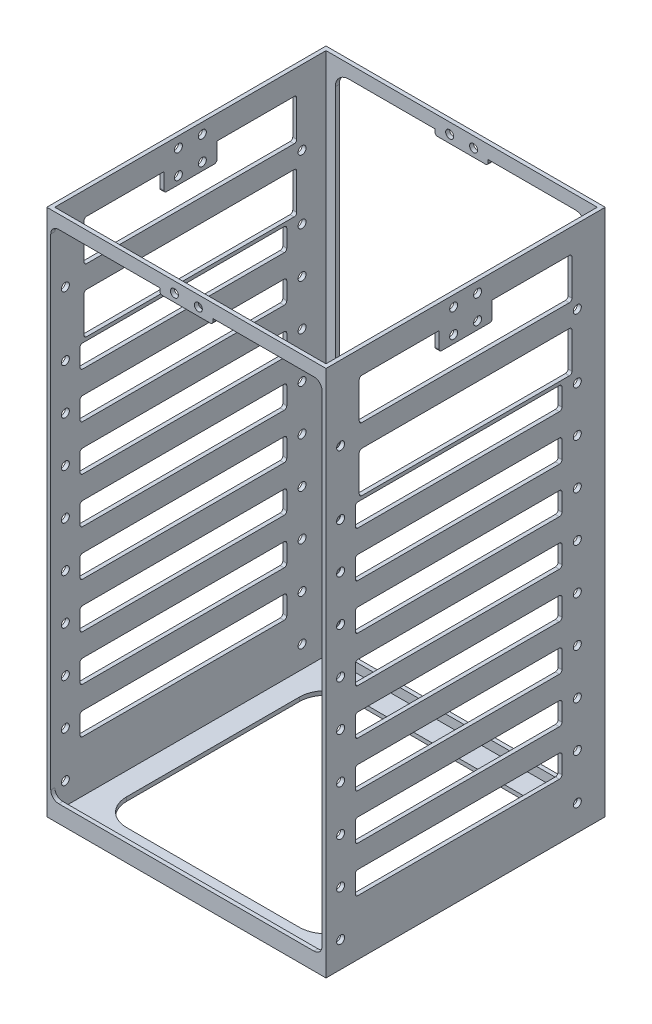
SolidWorks part; units mm, degrees
ref_plane "Front Plane" through (0, 0, 0) normal (0, 0, 1) x (1, 0, 0)
ref_plane "Top Plane" through (0, 0, 0) normal (0, 1, 0) x (1, 0, 0)
ref_plane "Right Plane" through (0, 0, 0) normal (1, 0, 0) x (0, 0, -1)
sketch "Sketch1" plane through (0, 0, 0) normal (0, 1, 0) x (1, 0, 0)
  line L1 (-52.5, -52.5) -> (52.5, -52.5)
  line L2 (-52.5, -52.5) -> (-52.5, 52.5)
  line L3 (-52.5, 52.5) -> (52.5, 52.5)
  line L4 (52.5, -52.5) -> (52.5, 52.5)
  line L5 (-52.5, -52.5) -> (52.5, 52.5) construction
  line L6 (-52.5, 52.5) -> (52.5, -52.5) construction
  line L7 (-32.5, -42.5) -> (32.5, -42.5)
  line L8 (-42.5, -32.5) -> (-42.5, 32.5)
  line L9 (-32.5, 42.5) -> (32.5, 42.5)
  line L10 (42.5, -32.5) -> (42.5, 32.5)
  line L11 (-42.5, -42.5) -> (42.5, 42.5) construction
  line L12 (-42.5, 42.5) -> (42.5, -42.5) construction
  arc A0 (32.5, -42.5) -> (42.5, -32.5) centre (32.5, -32.5) ccw
  arc A1 (32.5, 42.5) -> (42.5, 32.5) centre (32.5, 32.5) cw
  arc A2 (-42.5, 32.5) -> (-32.5, 42.5) centre (-32.5, 32.5) cw
  arc A3 (-32.5, -42.5) -> (-42.5, -32.5) centre (-32.5, -32.5) cw
  point P0 (0, 0)
  point P6 (0, 0)
  dimension "D3" = 10
  dimension "D1" = 105
  dimension "D2" = 42.5
extrude "Boss-Extrude2" add sketch "Sketch1" along normal blind 1.5 contours A3 L7 A0 L10 A1 L9 A2 L8 | L2 L1 L4 L3 region at (0, 0, 0)
sketch "Sketch3" plane through (0, 1.5, 0) normal (0, 1, 0) x (1, 0, 0)
  line L1 (-52.5, -52.5) -> (52.5, -52.5)
  line L2 (-52.5, -52.5) -> (-52.5, 52.5)
  line L3 (-52.5, 52.5) -> (52.5, 52.5)
  line L4 (52.5, -52.5) -> (52.5, 52.5)
  line L5 (-52.5, -52.5) -> (52.5, 52.5) construction
  line L6 (-52.5, 52.5) -> (52.5, -52.5) construction
  line L7 (-51, -51) -> (51, -51)
  line L8 (-51, -51) -> (-51, 51)
  line L9 (-51, 51) -> (51, 51)
  line L10 (51, -51) -> (51, 51)
  line L11 (-51, -51) -> (51, 51) construction
  line L12 (-51, 51) -> (51, -51) construction
  point P0 (0, 0)
  point P7 (0, 0)
  dimension "D1" = 1.5
extrude "Boss-Extrude3" add sketch "Sketch3" along normal blind 197 contours L8 L7 L10 L9 | L2 L3 L4 L1
sketch "Sketch4" plane through (0, 0, -52.5) normal (0, 0, 1) x (1, 0, 0)
  line L0 (-52.5, 0) -> (52.5, 0) construction
  line L1 (-42.5, 5) -> (42.5, 5)
  line L2 (-47.5, 10) -> (-47.5, 188.5)
  line L3 (-42.5, 193.5) -> (42.5, 193.5)
  line L4 (47.5, 10) -> (47.5, 188.5)
  line L5 (-47.5, 5) -> (47.5, 193.5) construction
  line L6 (-47.5, 193.5) -> (47.5, 5) construction
  line L7 (52.5, 198.5) -> (52.5, 0) construction
  line L8 (-51, 198.5) -> (51, 198.5) construction
  line L9 (-52.5, 198.5) -> (-52.5, 0) construction
  arc A0 (-42.5, 5) -> (-47.5, 10) centre (-42.5, 10) cw
  arc A1 (42.5, 5) -> (47.5, 10) centre (42.5, 10) ccw
  arc A2 (42.5, 193.5) -> (47.5, 188.5) centre (42.5, 188.5) cw
  arc A3 (-47.5, 188.5) -> (-42.5, 193.5) centre (-42.5, 188.5) cw
  point P0 (0, 99.25)
  dimension "D5" = 5
  dimension "D1" = 5
  dimension "D2" = 5
  dimension "D3" = 5
  dimension "D4" = 5
extrude "Cut-Extrude1" cut sketch "Sketch4" along normal up to surface (1.5 mm away) up to face at (0, 100, -51)
sketch "Sketch5" plane through (0, 0, 52.5) normal (0, 0, 1) x (1, 0, 0)
  line L0 (-52.5, 198.5) -> (52.5, 198.5) construction
  line L1 (-48, 6.5) -> (48, 6.5)
  line L2 (-51, 9.5) -> (-51, 190.5)
  line L3 (-48, 193.5) -> (48, 193.5)
  line L4 (51, 9.5) -> (51, 190.5)
  line L5 (-51, 6.5) -> (51, 193.5) construction
  line L6 (-51, 193.5) -> (51, 6.5) construction
  line L7 (-52.5, 1.5) -> (52.5, 1.5) construction
  line L8 (-52.5, 198.5) -> (-52.5, 0) construction
  line L9 (52.5, 198.5) -> (52.5, 0) construction
  arc A0 (48, 6.5) -> (51, 9.5) centre (48, 9.5) ccw
  arc A1 (-48, 6.5) -> (-51, 9.5) centre (-48, 9.5) cw
  arc A2 (48, 193.5) -> (51, 190.5) centre (48, 190.5) cw
  arc A3 (-51, 190.5) -> (-48, 193.5) centre (-48, 190.5) cw
  point P0 (0, 100)
  dimension "D5" = 3
  dimension "D1" = 5
  dimension "D2" = 5
  dimension "D3" = 1.5
  dimension "D4" = 1.5
sketch "Sketch6" plane through (52.5, 0, 0) normal (1, 0, 0) x (0, 0, -1)
  line L0 (-52.5, 6.5) -> (-52.5, 193.5) construction
  line L2 (-52.5, 0) -> (52.5, 0) construction
  circle A0 centre (-47, 9.75) radius 1.5
  circle A1 centre (42, 9.75) radius 1.5
  circle A2 centre (-47, 26.85) radius 1.5
  circle A3 centre (42, 26.85) radius 1.5
  circle A4 centre (-47, 43.95) radius 1.5
  circle A5 centre (42, 43.95) radius 1.5
  circle A6 centre (-47, 61.05) radius 1.5
  circle A7 centre (42, 61.05) radius 1.5
  circle A8 centre (-47, 78.15) radius 1.5
  circle A9 centre (42, 78.15) radius 1.5
  circle A10 centre (-47, 95.25) radius 1.5
  circle A11 centre (42, 95.25) radius 1.5
  circle A12 centre (-47, 112.35) radius 1.5
  circle A13 centre (42, 112.35) radius 1.5
  circle A14 centre (-47, 129.45) radius 1.5
  circle A15 centre (42, 129.45) radius 1.5
  circle A16 centre (-47, 146.55) radius 1.5
  circle A17 centre (42, 146.55) radius 1.5
  circle A18 centre (-47, 170.55) radius 1.5
  circle A19 centre (42, 170.55) radius 1.5
  dimension "D4" = 3
  dimension "D5" = 3
  dimension "D1" = 5.5
  dimension "D2" = 89
  dimension "D3" = 9.75
  dimension "D7" = 17.1
  dimension "D9" = 24
  dimension "D6" = 9
  dimension "D8" = 2
extrude "Cut-Extrude2" cut sketch "Sketch6" against normal through all
extrude "Cut-Extrude3" cut sketch "Sketch5" against normal up to surface (1.5 mm away) up to face at (0, 100, 51)
sketch "Sketch7" plane through (52.5, 0, 0) normal (1, 0, 0) x (0, 0, -1)
  line L0 (-41.5, 38.95) -> (-41.5, 45.45)
  line L1 (-40.5, 20.85) -> (35.25, 20.85)
  line L2 (-41.5, 21.85) -> (-41.5, 28.35)
  line L3 (-40.5, 29.35) -> (35.25, 29.35)
  line L4 (36.25, 21.85) -> (36.25, 28.35)
  line L5 (-41.5, 20.85) -> (36.25, 29.35) construction
  line L6 (-41.5, 29.35) -> (36.25, 20.85) construction
  line L8 (-40.5, 37.95) -> (35.25, 37.95)
  line L9 (36.25, 38.95) -> (36.25, 45.45)
  line L10 (-40.5, 46.45) -> (35.25, 46.45)
  line L11 (-41.5, 56.05) -> (-41.5, 62.55)
  line L12 (-40.5, 55.05) -> (35.25, 55.05)
  line L13 (36.25, 56.05) -> (36.25, 62.55)
  line L14 (-40.5, 63.55) -> (35.25, 63.55)
  line L15 (-41.5, 73.15) -> (-41.5, 79.65)
  line L16 (-40.5, 72.15) -> (35.25, 72.15)
  line L17 (36.25, 73.15) -> (36.25, 79.65)
  line L18 (-40.5, 80.65) -> (35.25, 80.65)
  line L19 (-41.5, 90.25) -> (-41.5, 96.75)
  line L20 (-40.5, 89.25) -> (35.25, 89.25)
  line L21 (36.25, 90.25) -> (36.25, 96.75)
  line L22 (-40.5, 97.75) -> (35.25, 97.75)
  line L23 (-41.5, 107.35) -> (-41.5, 113.85)
  line L24 (-40.5, 106.35) -> (35.25, 106.35)
  line L25 (36.25, 107.35) -> (36.25, 113.85)
  line L26 (-40.5, 114.85) -> (35.25, 114.85)
  line L27 (-41.5, 124.45) -> (-41.5, 130.95)
  line L28 (-40.5, 123.45) -> (35.25, 123.45)
  line L29 (36.25, 124.45) -> (36.25, 130.95)
  line L30 (-40.5, 131.95) -> (35.25, 131.95)
  line L31 (-41.5, 141.55) -> (-41.5, 148.05)
  line L32 (-40.5, 140.55) -> (35.25, 140.55)
  line L33 (36.25, 141.55) -> (36.25, 148.05)
  line L34 (-40.5, 149.05) -> (35.25, 149.05)
  circle A0 centre (-47, 9.75) radius 1.5 construction
  arc A1 (35.25, 29.35) -> (36.25, 28.35) centre (35.25, 28.35) cw
  arc A2 (35.25, 20.85) -> (36.25, 21.85) centre (35.25, 21.85) ccw
  arc A3 (-40.5, 20.85) -> (-41.5, 21.85) centre (-40.5, 21.85) cw
  arc A4 (-41.5, 28.35) -> (-40.5, 29.35) centre (-40.5, 28.35) cw
  arc A5 (-41.5, 45.45) -> (-40.5, 46.45) centre (-40.5, 45.45) cw
  arc A6 (-40.5, 37.95) -> (-41.5, 38.95) centre (-40.5, 38.95) cw
  arc A7 (35.25, 37.95) -> (36.25, 38.95) centre (35.25, 38.95) ccw
  arc A8 (35.25, 46.45) -> (36.25, 45.45) centre (35.25, 45.45) cw
  arc A9 (-41.5, 62.55) -> (-40.5, 63.55) centre (-40.5, 62.55) cw
  arc A10 (-40.5, 55.05) -> (-41.5, 56.05) centre (-40.5, 56.05) cw
  arc A11 (35.25, 55.05) -> (36.25, 56.05) centre (35.25, 56.05) ccw
  arc A12 (35.25, 63.55) -> (36.25, 62.55) centre (35.25, 62.55) cw
  arc A13 (-41.5, 79.65) -> (-40.5, 80.65) centre (-40.5, 79.65) cw
  arc A14 (-40.5, 72.15) -> (-41.5, 73.15) centre (-40.5, 73.15) cw
  arc A15 (35.25, 72.15) -> (36.25, 73.15) centre (35.25, 73.15) ccw
  arc A16 (35.25, 80.65) -> (36.25, 79.65) centre (35.25, 79.65) cw
  arc A17 (-41.5, 96.75) -> (-40.5, 97.75) centre (-40.5, 96.75) cw
  arc A18 (-40.5, 89.25) -> (-41.5, 90.25) centre (-40.5, 90.25) cw
  arc A19 (35.25, 89.25) -> (36.25, 90.25) centre (35.25, 90.25) ccw
  arc A20 (35.25, 97.75) -> (36.25, 96.75) centre (35.25, 96.75) cw
  arc A21 (-41.5, 113.85) -> (-40.5, 114.85) centre (-40.5, 113.85) cw
  arc A22 (-40.5, 106.35) -> (-41.5, 107.35) centre (-40.5, 107.35) cw
  arc A23 (35.25, 106.35) -> (36.25, 107.35) centre (35.25, 107.35) ccw
  arc A24 (35.25, 114.85) -> (36.25, 113.85) centre (35.25, 113.85) cw
  arc A25 (-41.5, 130.95) -> (-40.5, 131.95) centre (-40.5, 130.95) cw
  arc A26 (-40.5, 123.45) -> (-41.5, 124.45) centre (-40.5, 124.45) cw
  arc A27 (35.25, 123.45) -> (36.25, 124.45) centre (35.25, 124.45) ccw
  arc A28 (35.25, 131.95) -> (36.25, 130.95) centre (35.25, 130.95) cw
  arc A29 (-41.5, 148.05) -> (-40.5, 149.05) centre (-40.5, 148.05) cw
  arc A30 (-40.5, 140.55) -> (-41.5, 141.55) centre (-40.5, 141.55) cw
  arc A31 (35.25, 140.55) -> (36.25, 141.55) centre (35.25, 141.55) ccw
  arc A32 (35.25, 149.05) -> (36.25, 148.05) centre (35.25, 148.05) cw
  circle A35 centre (42, 9.75) radius 1.5 construction
  point P0 (-2.625, 25.1)
  dimension "D5" = 1
  dimension "D3" = 5.75
  dimension "D1" = 8.5
  dimension "D2" = 11.1
  dimension "D4" = 5.5
  dimension "D7" = 8.6
  dimension "D6" = 8
extrude "Cut-Extrude4" cut sketch "Sketch7" against normal through all
sketch "Sketch8" plane through (52.5, 0, 0) normal (1, 0, 0) x (0, 0, -1)
  line L1 (-39, 150.35) -> (39, 150.35)
  line L2 (-40, 151.35) -> (-40, 164.75)
  line L3 (-39, 165.75) -> (39, 165.75)
  line L4 (40, 151.35) -> (40, 164.75)
  line L5 (-40, 150.35) -> (40, 165.75) construction
  line L6 (-40, 165.75) -> (40, 150.35) construction
  line L7 (52.5, 198.5) -> (52.5, 0) construction
  line L8 (-40, 189.55) -> (40, 174.15) construction
  line L9 (-40, 175.15) -> (-40, 188.55)
  line L10 (-39, 174.15) -> (39, 174.15)
  line L11 (40, 175.15) -> (40, 188.55)
  line L12 (-39, 189.55) -> (39, 189.55)
  circle A0 centre (-47, 146.55) radius 1.5 construction
  arc A2 (-40, 164.75) -> (-39, 165.75) centre (-39, 164.75) cw
  arc A3 (39, 165.75) -> (40, 164.75) centre (39, 164.75) cw
  arc A4 (39, 150.35) -> (40, 151.35) centre (39, 151.35) ccw
  arc A5 (-39, 150.35) -> (-40, 151.35) centre (-39, 151.35) cw
  arc A6 (-39, 174.15) -> (-40, 175.15) centre (-39, 175.15) cw
  arc A7 (-40, 188.55) -> (-39, 189.55) centre (-39, 188.55) cw
  arc A8 (39, 174.15) -> (40, 175.15) centre (39, 175.15) ccw
  arc A9 (39, 189.55) -> (40, 188.55) centre (39, 188.55) cw
  point P0 (0, 158.05)
  dimension "D5" = 1
  dimension "D1" = 3.8
  dimension "D2" = 15.4
  dimension "D3" = 80
  dimension "D4" = 12.5
  dimension "D7" = 8.4
  dimension "D6" = 2
extrude "Cut-Extrude5" cut sketch "Sketch8" against normal through all
sketch "Sketch15" plane through (52.5, 0, 0) normal (1, 0, 0) x (0, 0, -1)
  line L0 (39, 189.55) -> (-39, 189.55) construction
  line L1 (-10, 189.55) -> (10, 189.55)
  line L2 (-10, 189.55) -> (-10, 183.55)
  line L3 (-9, 182.55) -> (9, 182.55)
  line L4 (10, 189.55) -> (10, 183.55)
  line L5 (-52.5, 198.5) -> (-52.5, 0) construction
  arc A0 (9, 182.55) -> (10, 183.55) centre (9, 183.55) ccw
  arc A1 (-10, 183.55) -> (-9, 182.55) centre (-9, 183.55) ccw
  dimension "D4" = 1
  dimension "D1" = 20
  dimension "D2" = 7
  dimension "D3" = 42.5
extrude "Boss-Extrude4" add sketch "Sketch15" against normal up to surface (1.5 mm away) up to face at (51, 158.05, 0)
sketch "Sketch16" plane through (-52.5, 0, 0) normal (-1, 0, 0) x (0, 0, 1)
  line L1 (-10, 189.55) -> (10, 189.55)
  line L2 (-10, 189.55) -> (-10, 183.55)
  line L3 (-9, 182.55) -> (9, 182.55)
  line L4 (10, 189.55) -> (10, 183.55)
  arc A0 (9, 182.55) -> (10, 183.55) centre (9, 183.55) ccw
  arc A1 (-10, 183.55) -> (-9, 182.55) centre (-9, 183.55) ccw
  dimension "D3" = 1
  dimension "D1" = 7
  dimension "D2" = 20
extrude "Boss-Extrude5" add sketch "Sketch16" against normal up to surface (1.5 mm away) up to face at (-51, 158.05, 0)
sketch "Sketch9" plane through (52.5, 0, 0) normal (1, 0, 0) x (0, 0, -1)
  line L0 (-52.5, 198.5) -> (52.5, 198.5) construction
  line L1 (-52.5, 198.5) -> (-52.5, 0) construction
  line L2 (-10.0428, 190) -> (10.2919, 190) construction
  circle A0 centre (-4.5, 194.5) radius 1.5
  circle A1 centre (4.5, 194.5) radius 1.5
  circle A2 centre (4.5, 185.5) radius 1.5
  circle A3 centre (-4.5, 185.5) radius 1.5
  dimension "D1" = 3
  dimension "D3" = 9
  dimension "D5" = 3
  dimension "D2" = 4
  dimension "D4" = 48
  dimension "D6" = 4.5
extrude "Cut-Extrude6" cut sketch "Sketch9" against normal through all
sketch "Sketch17" plane through (0, 0, 52.5) normal (0, 0, 1) x (1, 0, 0)
  line L0 (48, 193.5) -> (-48, 193.5) construction
  line L1 (-10, 193.5) -> (10, 193.5)
  line L2 (-10, 193.5) -> (-10, 192.5)
  line L3 (-9, 191.5) -> (9, 191.5)
  line L4 (10, 193.5) -> (10, 192.5)
  line L5 (-52.5, 198.5) -> (-52.5, 0) construction
  arc A0 (9, 191.5) -> (10, 192.5) centre (9, 192.5) ccw
  arc A1 (-10, 192.5) -> (-9, 191.5) centre (-9, 192.5) ccw
  dimension "D4" = 1
  dimension "D1" = 20
  dimension "D2" = 42.5
  dimension "D3" = 2
extrude "Boss-Extrude6" add sketch "Sketch17" against normal up to surface (1.5 mm away) up to face at (0, 194.3738, 51)
sketch "Sketch18" plane through (0, 0, -52.5) normal (0, 0, -1) x (-1, 0, 0)
  line L1 (-10, 193.5) -> (10, 193.5)
  line L2 (-10, 193.5) -> (-10, 192.5)
  line L3 (-9, 191.5) -> (9, 191.5)
  line L4 (10, 193.5) -> (10, 192.5)
  arc A0 (9, 191.5) -> (10, 192.5) centre (9, 192.5) ccw
  arc A1 (-10, 192.5) -> (-9, 191.5) centre (-9, 192.5) ccw
  dimension "D3" = 1
  dimension "D1" = 2
  dimension "D2" = 20
extrude "Boss-Extrude7" add sketch "Sketch18" against normal up to surface (1.5 mm away) up to face at (0, 99.25, -51)
sketch "Sketch19" plane through (0, 0, 52.5) normal (0, 0, 1) x (1, 0, 0)
  line L0 (0, 198.5) -> (0, 191.5) construction
  line L1 (-9, 191.5) -> (9, 191.5) construction
  line L3 (-52.5, 198.5) -> (52.5, 198.5) construction
  circle A0 centre (-4.5, 194.5) radius 1.5
  circle A1 centre (4.5, 194.5) radius 1.5
  dimension "D1" = 3
  dimension "D2" = 4
  dimension "D3" = 4.5
extrude "Cut-Extrude7" cut sketch "Sketch19" against normal through all
